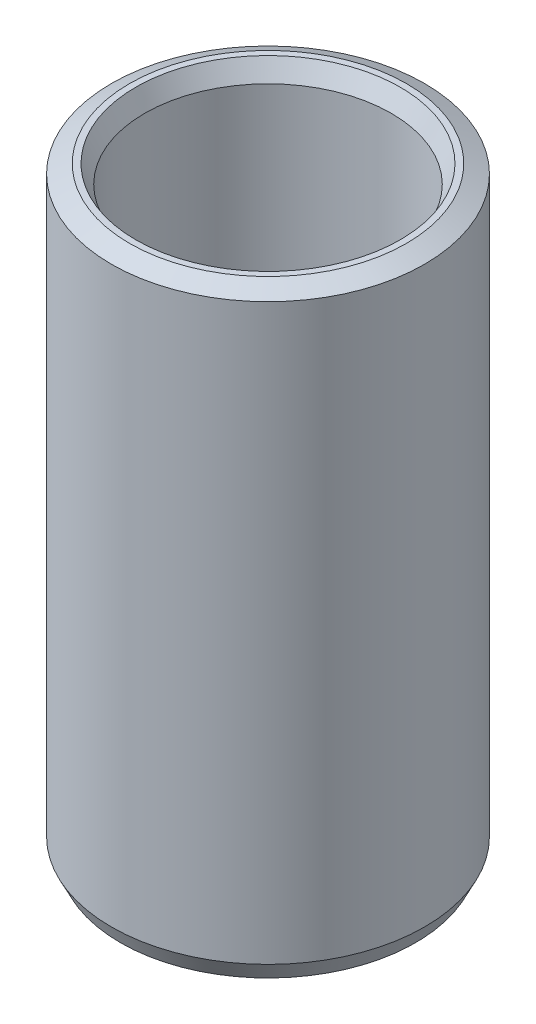
SolidWorks part; units mm, degrees
ref_plane "Front Plane" through (0, 0, 0) normal (0, 0, 1) x (1, 0, 0)
ref_plane "Top Plane" through (0, 0, 0) normal (0, 1, 0) x (1, 0, 0)
ref_plane "Right Plane" through (0, 0, 0) normal (1, 0, 0) x (0, 0, -1)
sketch "Sketch1" plane through (0, 0, 0) normal (0, 1, 0) x (1, 0, 0)
  circle A0 centre (0, 0) radius 57.5
  dimension "SLEEVE_OD" = 115
extrude "Boss-Extrude1" add sketch "Sketch1" along normal blind 220.7038
sketch "Sketch2" plane through (0, 0, 0) normal (0, 1, 0) x (1, 0, 0)
  circle A0 centre (0, 0) radius 45.2614
  dimension "BORE_D" = 90.5227
extrude "Cut-Extrude1" cut sketch "Sketch2" along normal through all
chamfer "Chamfer1" distance 3.2965 angle 63.657 4 edges at (0, 220.7038, 45.2614) (0, 0, 45.2614) (0, 0, 57.5) (0, 220.7038, 57.5) first distance on face at (0, 220.7038, 45.2614) first distance on face at (0, 0, 45.2614) first distance on face at (0, 220.7038, 57.5)
